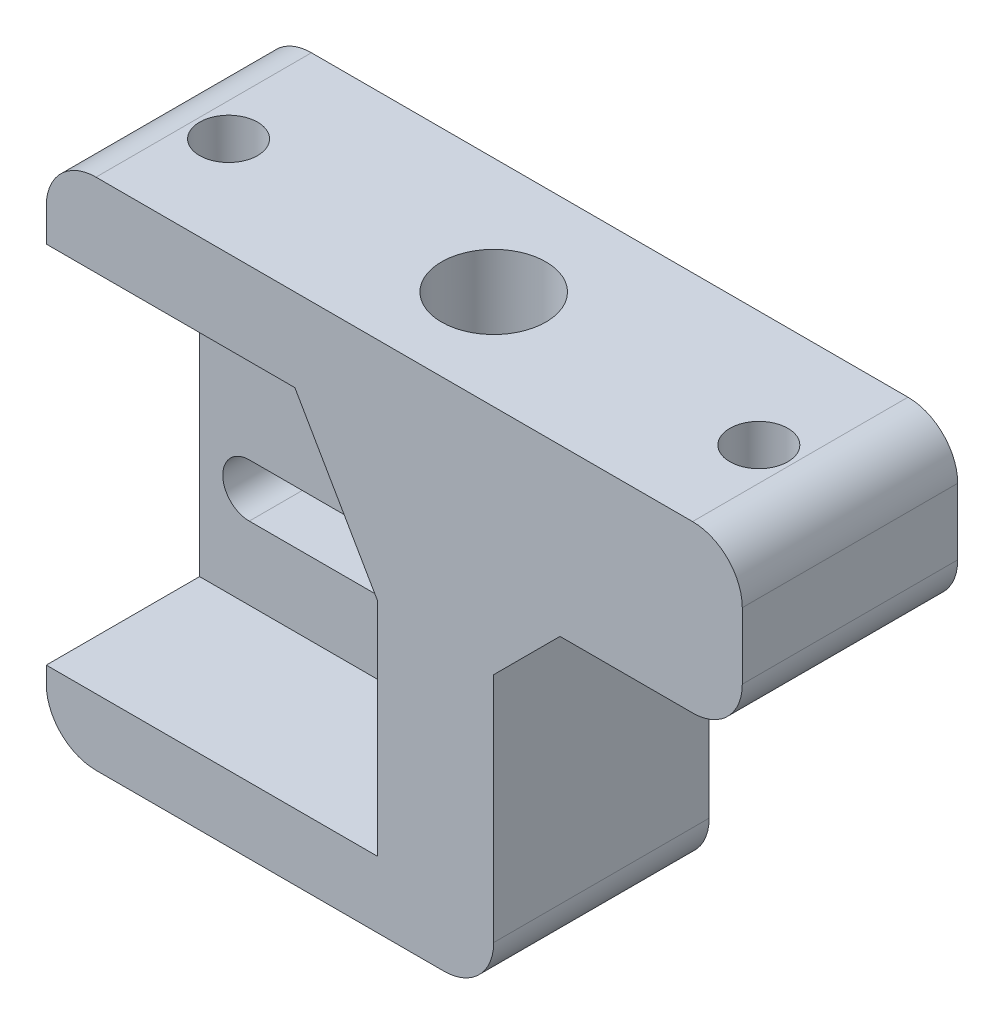
SolidWorks part; units mm, degrees
ref_plane "Plan de face" through (0, 0, 0) normal (0, 0, 1) x (1, 0, 0)
ref_plane "Plan de dessus" through (0, 0, 0) normal (0, 1, 0) x (1, 0, 0)
ref_plane "Plan de droite" through (0, 0, 0) normal (1, 0, 0) x (0, 0, -1)
sketch "Esquisse1" plane through (0, 0, 0) normal (0, 0, 1) x (1, 0, 0)
  line L1 (0, 0) -> (30, 0)
  line L2 (0, 0) -> (0, 40)
  line L3 (0, 40) -> (30, 40)
  line L4 (30, 0) -> (30, 40)
  dimension "D1" = 30
  dimension "D2" = 40
extrude "Boss.-Extru.1" add sketch "Esquisse1" along normal blind 14
sketch "Esquisse3" plane through (0, 40, 0) normal (0, 1, 0) x (1, 0, 0)
  line L0 (24, 0) -> (24, -14) construction
  line L3 (30, -14) -> (30, 0) construction
  line L4 (30, -14) -> (0, -14) construction
  line L5 (30, 0) -> (0, 0) construction
  circle A0 centre (24, -7) radius 3.15
  dimension "D1" = 6.3
  dimension "D2" = 6
extrude "Enlèv. mat.-Extru.1" cut sketch "Esquisse3" against normal blind 30
sketch "Esquisse4" plane through (0, 0, 14) normal (0, 0, 1) x (1, 0, 0)
  line L0 (0, 40) -> (0, 0) construction
  line L1 (0, 13) -> (15, 13)
  line L2 (0, 13) -> (0, 35)
  line L3 (0, 35) -> (15, 35)
  line L4 (15, 13) -> (15, 35)
  line L5 (30, 40) -> (0, 40) construction
  dimension "D1" = 15
  dimension "D2" = 22
  dimension "D3" = 5
extrude "Enlèv. mat.-Extru.2" cut sketch "Esquisse4" against normal blind 10.25
sketch "Esquisse5" plane through (0, 0, 3.75) normal (0, 0, 1) x (1, 0, 0)
  line L0 (15, 24) -> (0, 24) construction
  line L1 (15, 13) -> (15, 35) construction
  line L2 (0, 35) -> (0, 13) construction
  line L3 (10, 24) -> (10, 35) construction
  line L4 (15, 35) -> (0, 35) construction
  line L5 (6, 29) -> (14, 29) construction
  line L6 (6, 30.6) -> (14, 30.6)
  line L7 (6, 27.4) -> (14, 27.4)
  line L8 (6, 19) -> (14, 19) construction
  line L9 (6, 17.4) -> (14, 17.4)
  line L10 (6, 20.6) -> (14, 20.6)
  arc A0 (6, 30.6) -> (6, 27.4) centre (6, 29) ccw
  arc A1 (6, 17.4) -> (6, 20.6) centre (6, 19) cw
  arc A2 (14, 27.4) -> (14, 30.6) centre (14, 29) ccw
  arc A3 (14, 20.6) -> (14, 17.4) centre (14, 19) cw
  point P14 (10, 29)
  point P19 (10, 19)
  dimension "D2" = 5
  dimension "D3" = 10
  dimension "D1" = 1.6
  dimension "D4" = 8
extrude "Enlèv. mat.-Extru.3" cut sketch "Esquisse5" against normal through all
sketch "Esquisse6" plane through (0, 0, 14) normal (0, 0, 1) x (1, 0, 0)
  line L0 (15, 35) -> (18, 35)
  line L1 (15, 13) -> (15, 17.751) construction
  line L2 (23, 26.3397) -> (23, 13)
  line L3 (23, 13) -> (15, 13)
  line L4 (15, 13) -> (15, 35)
  line L5 (15, 13) -> (15, 35) construction
  line L6 (15, 35) -> (0, 35) construction
  line L7 (18, 35) -> (23, 26.3397)
  dimension "D1" = 30
  dimension "D2" = 3
  dimension "D3" = 8
extrude "Enlèv. mat.-Extru.4" cut sketch "Esquisse6" against normal up to surface (10.25 mm away) up to face at (10.4325, 24, 3.75)
sketch "Esquisse7" plane through (0, 0, 14) normal (0, 0, 1) x (1, 0, 0)
  line L0 (0, 6.5) -> (30, 6.5) construction
  line L1 (0, 13) -> (0, 0) construction
  line L2 (30, 0) -> (30, 40) construction
  line L3 (15, 6.5) -> (15, 0) construction
  line L4 (0, 0) -> (30, 0) construction
  circle A0 centre (5, 6.5) radius 1.75
  circle A1 centre (25, 6.5) radius 1.75
  dimension "D1" = 3.5
  dimension "D2" = 10
extrude "Enlèv. mat.-Extru.5" cut sketch "Esquisse7" against normal through all
sketch "Esquisse9" plane through (0, 40, 0) normal (0, 1, 0) x (1, 0, 0)
  line L0 (0, -14) -> (0, 0) construction
  line L1 (30, -14) -> (0, -14)
  line L2 (30, -14) -> (30, -13)
  line L3 (30, -13) -> (0, -13)
  line L4 (0, -14) -> (0, -13)
  dimension "D1" = 1
extrude "Enlèv. mat.-Extru.9" cut sketch "Esquisse9" against normal up to vertex (40 mm away) up to point (0, 0, 14)
sketch "Esquisse11" plane through (0, 0, 13) normal (0, 0, 1) x (1, 0, 0)
  line L0 (30, 0) -> (30, 40) construction
  line L1 (0, 0) -> (30, 0)
  line L2 (0, 0) -> (0, 9)
  line L3 (0, 9) -> (30, 9)
  line L4 (30, 0) -> (30, 9)
  dimension "D1" = 9
extrude "Enlèv. mat.-Extru.10" cut sketch "Esquisse11" against normal up to vertex (13 mm away) up to point (30, 0, 0)
sketch "Esquisse12" plane through (0, 40, 0) normal (0, 1, 0) x (1, 0, 0)
  line L0 (30, 0) -> (0, 0) construction
  line L1 (30, -13) -> (45, -13)
  line L2 (30, -13) -> (30, 0)
  line L3 (30, 0) -> (45, 0)
  line L4 (45, -13) -> (45, 0)
  dimension "D1" = 15
extrude "Boss.-Extru.2" add sketch "Esquisse12" against normal blind 10
sketch "Esquisse13" plane through (0, 40, 0) normal (0, 1, 0) x (1, 0, 0)
  line L0 (24, -7) -> (40, -7) construction
  line L1 (24, -7) -> (24, -1.0006) construction
  circle A0 centre (40, -7) radius 1.75
  circle A1 centre (8, -7) radius 1.75
  dimension "D1" = 3.5
  dimension "D2" = 16
extrude "Enlèv. mat.-Extru.11" cut sketch "Esquisse13" against normal blind 12
chamfer "Chanfrein1" distance 4 angle 45 1 edges at (30, 30, 6.5)
sketch "Esquisse14" plane through (0, 0, 13) normal (0, 0, 1) x (1, 0, 0)
  line L0 (45, 40) -> (0, 40) construction
  line L1 (0, 9) -> (3, 9)
  line L2 (0, 9) -> (0, 40)
  line L3 (0, 40) -> (3, 40)
  line L4 (3, 9) -> (3, 40)
  dimension "D1" = 3
extrude "Enlèv. mat.-Extru.12" cut sketch "Esquisse14" against normal through all both and the other way through all
fillet "Congé1" radius 3 5 edges at (45, 40, 6.5) (45, 30, 6.5) (30, 9, 6.5) (3, 9, 6.5) (3, 40, 6.5)
